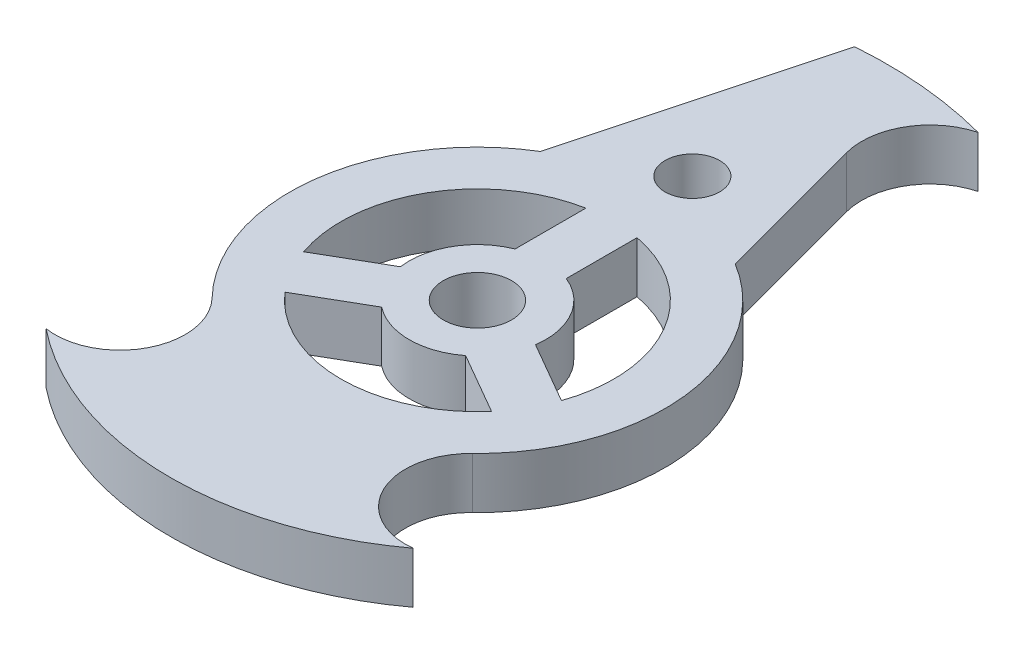
SolidWorks part; units mm, degrees
material "AISI Type A2 Tool Steel"
ref_plane "Front Plane" through (0, 0, 0) normal (0, 0, 1) x (1, 0, 0)
ref_plane "Top Plane" through (0, 0, 0) normal (0, 1, 0) x (1, 0, 0)
ref_plane "Right Plane" through (0, 0, 0) normal (1, 0, 0) x (0, 0, -1)
other "Center of Mass"
other "Bounding Box"
ref_plane "Default Plane" through (-8.9266, -12.7485, 0) normal (-0.1736, 0.9848, 0) x (0.9848, 0.1736, 0)
sketch "Sketch1" plane through (0, 0, 0) normal (0, 1, 0) x (1, 0, 0)
  circle A0 centre (0, 0) radius 6.35
  circle A1 centre (0, 0) radius 34.925
  circle A2 centre (0, 0) radius 76.2 construction
  dimension "D1" = 12.7
  dimension "D2" = 152.4
  dimension "D3" = 69.85
extrude "Boss-Extrude1" add sketch "Sketch1" along normal mid plane 9.525
sketch "Sketch2" plane through (0, 4.7625, 0) normal (0, 1, 0) x (1, 0, 0)
  line L0 (-18.1431, 29.8427) -> (-5.7805, 75.9804)
  line L1 (18.1431, 29.8427) -> (10.5677, 58.1143)
  line L2 (-5.7805, 75.9804) -> (19.5132, 73.6592) construction
  line L3 (0, 0) -> (0, 76.2) construction
  line L4 (0, 0) -> (19.5132, 73.6592) construction
  line L5 (19.5132, 73.6592) -> (-54.0341, 53.7285) construction
  line L6 (-18.1431, 29.8427) -> (0, 29.8427) construction
  line L7 (0, 29.8427) -> (18.1431, 29.8427) construction
  line L8 (-5.7805, 75.9804) -> (0, 97.5536) construction
  line L9 (0, 97.5536) -> (10.5677, 58.1143) construction
  circle A0 centre (0, 0) radius 34.925 construction
  circle A1 centre (0, 0) radius 76.2 construction
  arc A2 (-5.7805, 75.9804) -> (19.5132, 73.6592) centre (0, 0) cw
  arc A3 (10.5677, 58.1143) -> (19.5132, 73.6592) centre (22.835, 61.4013) cw
  arc A4 (18.1431, 29.8427) -> (-18.1431, 29.8427) centre (0, 0) ccw
  circle A5 centre (0, 0) radius 34.925 construction
  point P12 (0, 0)
  point P14 (13.552, 32.1885)
  point P16 (-3.7467, 76.2)
  dimension "D1" = 60
  dimension "D3" = 12.7
  dimension "D2" = 25.4
  dimension "D4" = 30
extrude "Boss-Extrude2" add sketch "Sketch2" against normal up to surface (9.525 mm away) up to face at (0, -4.7625, 34.925)
sketch "Sketch3" plane through (0, 4.7625, 0) normal (0, 1, 0) x (1, 0, 0)
  line L0 (-35.5767, -44.7261) -> (0, 0) construction
  line L1 (0, 0) -> (33.9941, -45.9404) construction
  line L2 (0, 0) -> (0, -76.2) construction
  line L3 (0, 0) -> (-1.3299, -76.1884) construction
  line L4 (-35.5767, -44.7261) -> (49.9863, -57.5135) construction
  arc A0 (-35.5767, -44.7261) -> (33.9941, -45.9404) centre (0, 0) ccw
  arc A1 (-35.5767, -44.7261) -> (-25.0811, -24.3042) centre (-33.7852, -32.7388) ccw
  circle A2 centre (0, 0) radius 34.925 construction
  arc A3 (33.9941, -45.9404) -> (24.2176, -25.1648) centre (32.6221, -33.8979) cw
  arc A4 (-25.0811, -24.3042) -> (24.2176, -25.1648) centre (0, 0) ccw
  circle A5 centre (0, 0) radius 76.2 construction
  point P6 (-0.9974, -57.1413)
  dimension "D1" = 57.15
  dimension "D2" = 75
  dimension "D3" = 1
  dimension "D4" = 60
extrude "Boss-Extrude3" add sketch "Sketch3" against normal up to surface (9.525 mm away) up to face at (4.237, -4.7625, -41.1164)
sketch "Sketch4" plane through (0, 4.7625, 0) normal (0, 1, 0) x (1, 0, 0)
  line L0 (12.5772, -1.7622) -> (23.9882, -8.3503)
  line L1 (4.7625, 11.7732) -> (4.7625, 24.9495)
  line L2 (0, 0) -> (30.2459, -17.4625) construction
  line L3 (0, 0) -> (0, 34.925) construction
  line L4 (4.7625, 24.9495) -> (0, 24.9495) construction
  line L5 (23.9882, -8.3503) -> (21.6069, -12.4748) construction
  arc A0 (4.7625, 11.7732) -> (12.5772, -1.7622) centre (0, 0) cw
  arc A1 (4.7625, 24.9495) -> (23.9882, -8.3503) centre (0, 0) cw
  circle A2 centre (0, 0) radius 34.925 construction
  point P6 (-18.9079, -33.0772)
  point P12 (33.8206, -17.5435)
  dimension "D2" = 9.525
  dimension "D3" = 12.7
  dimension "D1" = 4.7625
  dimension "D4" = 120
extrude "Cut-Extrude1" cut sketch "Sketch4" against normal through all
pattern_circular "CirPattern1" count 3 over 360 about axis through (0, 4.7625, 0) along (0, -1, 0) of "Cut-Extrude1" reverse direction yes
sketch "Sketch5" plane through (0, 4.7625, 0) normal (0, 1, 0) x (1, 0, 0)
  line L0 (0, 0) -> (0, 76.2) construction
  circle A0 centre (0, 40.005) radius 5.08
  arc A1 (18.1431, 29.8427) -> (-18.1431, 29.8427) centre (0, 0) ccw construction
  point P2 (0, 47.7478)
  dimension "D1" = 10.16
extrude "Cut-Extrude2" cut sketch "Sketch5" against normal through all
